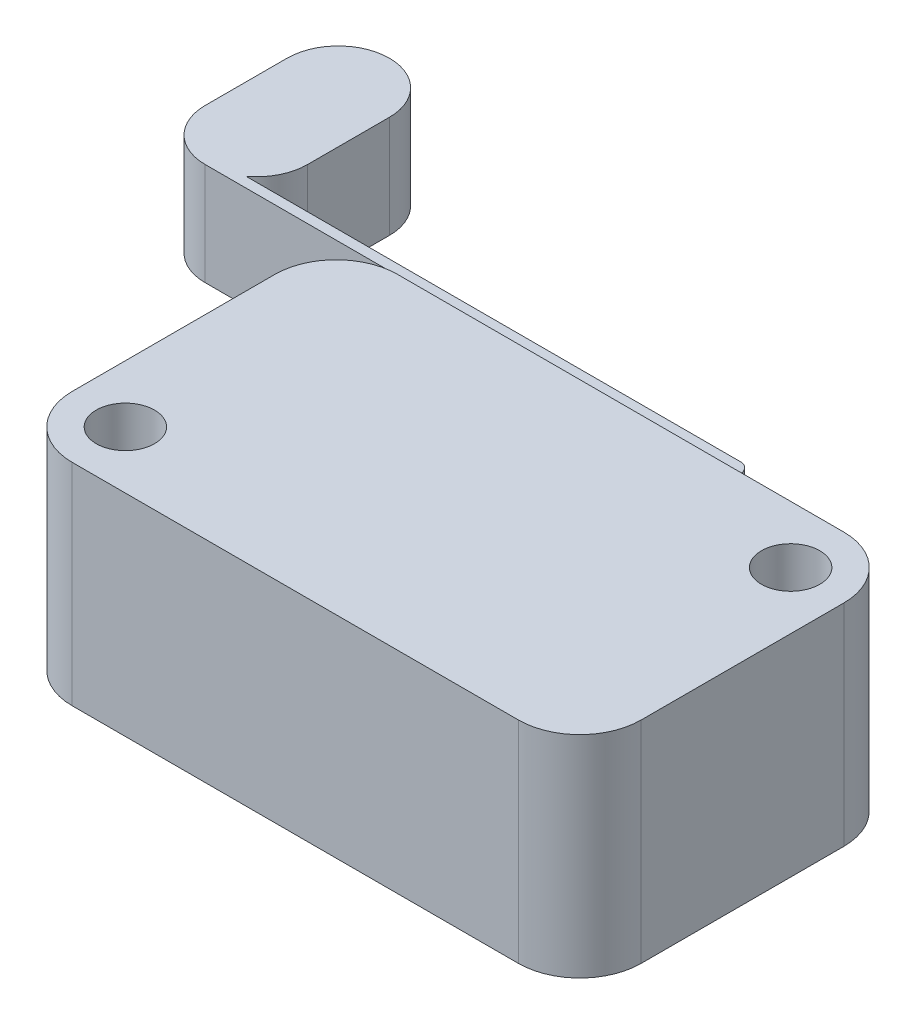
SolidWorks part; units mm, degrees
ref_plane "Front Plane" through (0, 0, 0) normal (0, 0, 1) x (1, 0, 0)
ref_plane "Top Plane" through (0, 0, 0) normal (0, 1, 0) x (1, 0, 0)
ref_plane "Right Plane" through (0, 0, 0) normal (1, 0, 0) x (0, 0, -1)
sketch "Sketch1" plane through (0, 0, 0) normal (0, 1, 0) x (1, 0, 0)
  line L0 (63.9515, 175.0782) -> (397.8985, 175.0782) construction
  line L1 (-22.2, -10.3) -> (0, 0) construction
  line L2 (-25, 2.8) -> (-8.1, 2.8)
  line L3 (-25, 2.8) -> (-25, -13.1)
  line L4 (-25, -13.1) -> (2.8, -13.1)
  line L5 (2.8, 2.8) -> (2.8, -13.1)
  line L6 (-25, 2.8) -> (2.8, -13.1) construction
  line L7 (-8.1, 2.8) -> (-8.1, 5.65) construction
  line L8 (-8.1, 5.65) -> (-35.0897, 5.65) construction
  line L9 (-7.85, 2.8) -> (-7.85, 5.9)
  line L10 (-7.85, 5.9) -> (-32.5, 5.9)
  line L11 (-8.35, 2.8) -> (-8.35, 5.4)
  line L12 (-8.35, 5.4) -> (-34, 5.4)
  line L13 (-8.1, 5.65) -> (-35.8536, 5.65) construction
  line L14 (-7.85, 5.9) -> (-35.8536, 5.9) construction
  line L15 (-8.35, 5.4) -> (-35.8536, 5.4) construction
  line L16 (-8.1, 2.8) -> (2.8, 2.8)
  line L17 (-34, 7.9) -> (-34, 11.9) construction
  line L18 (-36.5, 7.9) -> (-36.5, 11.9)
  line L19 (-31.5, 7.9) -> (-31.5, 11.9)
  circle A0 centre (0, 0) radius 1.425
  circle A1 centre (-22.2, -10.3) radius 1.425
  arc A2 (-32.5, 5.9) -> (-34, 5.4) centre (-34, 7.9) ccw construction
  arc A3 (-36.5, 7.9) -> (-31.5, 7.9) centre (-34, 7.9) ccw
  arc A4 (-31.5, 11.9) -> (-36.5, 11.9) centre (-34, 11.9) ccw
  point P9 (-11.1, -5.15)
  point P12 (-11.1, -5.15)
  point P16 (-34, 10.4)
  point P25 (-34, 9.9)
  dimension "D1" = 2.85
  dimension "D8" = 5
  dimension "D2" = 22.2
  dimension "D3" = 10.3
  dimension "D4" = 15.9
  dimension "D5" = 27.8
  dimension "D6" = 34
  dimension "D7" = 20.7
  dimension "D9" = 8.1
  dimension "D12" = 4
  dimension "D10" = 0.25
  dimension "D11" = 0.25
extrude "Boss-Extrude1" add sketch "Sketch1" along normal mid plane 10.3 contours L16 L2 L3 L4 L5 A1 A0 region at (-11.1, 0, 5.15)
fillet "Fillet1" radius 3 4 edges at (2.8, 0, -2.8) (2.8, 0, 13.1) (-25, 0, -2.8) (-25, 0, 13.1)
extrude "Boss-Extrude2" add sketch "Sketch1<4>" along normal mid plane 5 contours L10 A2 L12 L11 L2 L16 L9 | L19 A4 L18 A3 region at (-19.2616, 0, -5.5029) region at (-34, 0, -9.9)
sketch "Sketch1<4>" plane through (0, 0, 0) normal (0, 1, 0) x (1, 0, 0) same geometry as "Sketch1"
fillet "Fillet2" radius 0.5 2 edges at (-7.85, 0, -5.9) (-8.35, 0, -5.4)
ref_axis "Axis1" through (-34, 2.5, -7.9) along (0, -1, 0)
ref_plane "Plane1" through (-11.1, 0, 0) normal (1, 0, 0) x (0, 0, -1)
ref_plane "Plane2" through (-34, 0, 0) normal (1, 0, 0) x (0, 0, -1)
ref_plane "Plane3" through (-16.85, 0, 0) normal (1, 0, 0) x (0, 0, -1)
